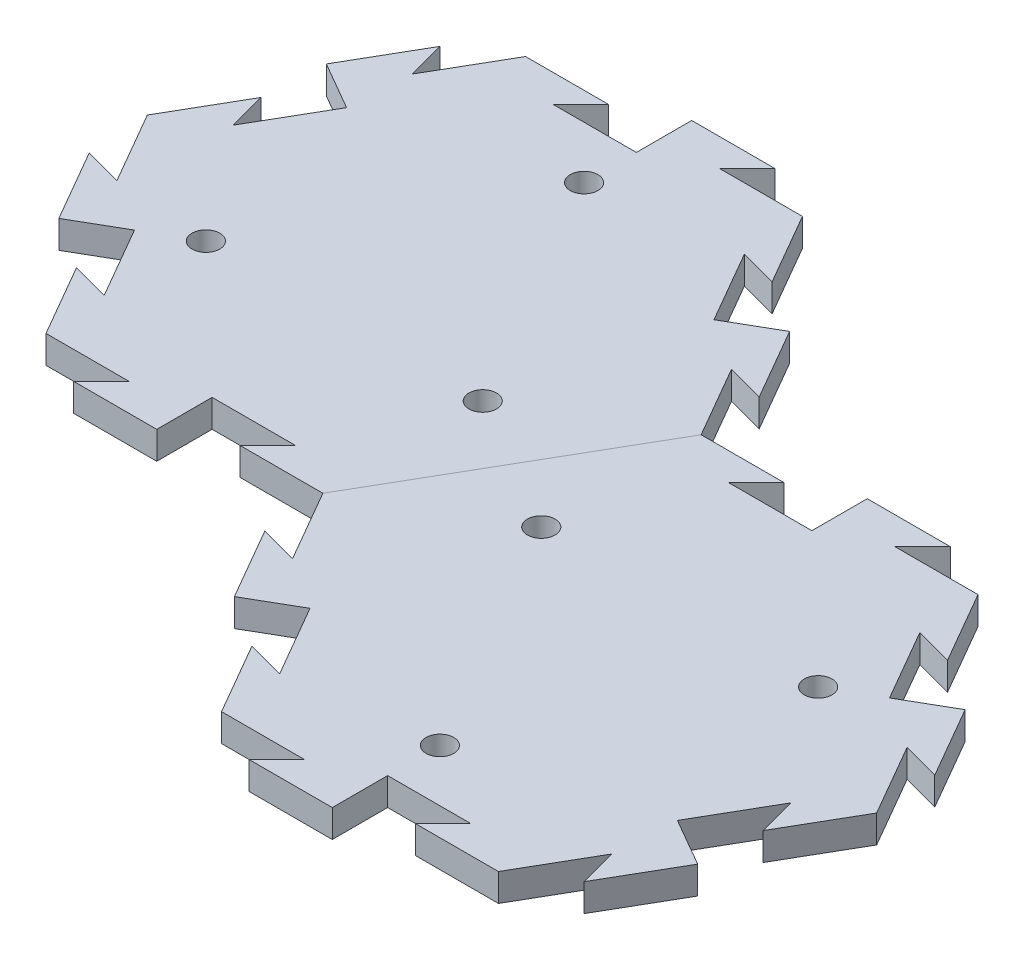
SolidWorks part; units mm, degrees
material "Cedar"
ref_plane "Front Plane" through (0, 0, 0) normal (0, 0, 1) x (1, 0, 0)
ref_plane "Top Plane" through (0, 0, 0) normal (0, 1, 0) x (1, 0, 0)
ref_plane "Right Plane" through (0, 0, 0) normal (1, 0, 0) x (0, 0, -1)
sketch "Sketch1" plane through (0, 0, 0) normal (0, 1, 0) x (1, 0, 0)
  line L0 (0, 0) -> (63.5, 0) construction
  line L1 (63.5, 0) -> (31.75, 54.9926)
  line L2 (31.75, 54.9926) -> (-31.75, 54.9926)
  line L3 (-31.75, 54.9926) -> (-63.5, 0)
  line L4 (-63.5, 0) -> (-31.75, -54.9926)
  line L5 (-31.75, -54.9926) -> (31.75, -54.9926)
  line L6 (31.75, -54.9926) -> (63.5, 0)
  circle A0 centre (0, 0) radius 54.9926 construction
  dimension "D1" = 63.5
extrude "Boss-Extrude1" add sketch "Sketch1" against normal blind 6.35
sketch "Sketch2" plane through (0, 0, 0) normal (0, 1, 0) x (1, 0, 0)
  point P1 (0, 0)
ref_axis "Axis1" through (0, 0, 0) along (0, 1, 0)
sketch "Sketch9" plane through (0, 0, 0) normal (0, 1, 0) x (1, 0, 0)
  line L1 (31.75, -18.3309) -> (0, 36.6617) construction
  line L2 (0, 36.6617) -> (-31.75, -18.3309) construction
  line L3 (-31.75, -18.3309) -> (31.75, -18.3309) construction
  circle A0 centre (0, 0) radius 18.3309 construction
  circle A1 centre (-31.75, -18.3309) radius 3.175
  dimension "D2" = 6.35
  dimension "D1" = 63.5
extrude "Cut-Extrude3" cut sketch "Sketch9" against normal through all
pattern_circular "CirPattern6" count 3 over 360 about axis through (0, 0, 0) along (0, 1, 0) of "Cut-Extrude3"
mirror "Mirror3" about plane through (31.75, -6.35, 54.9926) normal (0.866, 0, 0.5) of bodies 121 125
sketch "Sketch10" plane through (0, 0, 0) normal (0, 1, 0) x (1, 0, 0)
  line L0 (31.75, 54.9926) -> (41.275, 38.4948) construction
  line L1 (41.275, 38.4948) -> (32.6007, 40.8191)
  line L2 (32.6007, 40.8191) -> (42.1257, 24.3213)
  line L3 (42.1257, 24.3213) -> (47.625, 27.4963)
  line L4 (41.275, 38.4948) -> (47.625, 27.4963)
  line L5 (63.5, 0) -> (31.75, 54.9926) construction
  dimension "D1" = 45
  dimension "D2" = 6.35
extrude "Cut-Extrude4" cut sketch "Sketch10" against normal through all
sketch "Sketch11" plane through (0, 0, 0) normal (0, 1, 0) x (1, 0, 0)
  line L0 (47.625, 27.4963) -> (63.5, 0) construction
  line L1 (47.625, 27.4963) -> (53.1243, 30.6713)
  line L2 (53.1243, 30.6713) -> (62.6493, 14.1735)
  line L3 (62.6493, 14.1735) -> (53.975, 16.4978)
  line L4 (53.975, 16.4978) -> (47.625, 27.4963)
  line L5 (53.975, 16.4978) -> (63.5, 0) construction
  line L6 (53.975, 16.4978) -> (63.5, 0) construction
  line L7 (63.5, 0) -> (47.625, 27.4963) construction
  line L8 (31.75, -54.9926) -> (63.5, 0) construction
  dimension "D1" = 45
  dimension "D2" = 6.35
extrude "Boss-Extrude4" add sketch "Sketch11" against normal blind 6.35
pattern_circular "CirPattern7" count 6 over 360 about axis through (0, 0, 0) along (0, 1, 0) skipping 5 of "Cut-Extrude4", "Boss-Extrude4"
sketch "Sketch12" plane through (0, 0, 0) normal (0, 1, 0) x (1, 0, 0)
  line L0 (127, 0) -> (63.5, -109.9852) construction
  point P4 (95.25, -54.9926)
ref_axis "Axis2" through (95.25, 0, 54.9926) along (0, 1, 0)
sketch "Sketch13" plane through (0, 0, 0) normal (0, 1, 0) x (1, 0, 0)
  line L0 (127, 0) -> (136.525, -16.4978) construction
  line L1 (136.525, -16.4978) -> (127.8507, -14.1735)
  line L2 (127.8507, -14.1735) -> (137.3757, -30.6713)
  line L3 (137.3757, -30.6713) -> (142.875, -27.4963)
  line L4 (136.525, -16.4978) -> (142.875, -27.4963)
  line L5 (127, 0) -> (158.75, -54.9926) construction
  dimension "D1" = 45
  dimension "D2" = 6.35
extrude "Cut-Extrude5" cut sketch "Sketch13" against normal through all
sketch "Sketch14" plane through (0, 0, 0) normal (0, 1, 0) x (1, 0, 0)
  line L0 (142.875, -27.4963) -> (158.75, -54.9926) construction
  line L1 (142.875, -27.4963) -> (148.3743, -24.3213)
  line L2 (148.3743, -24.3213) -> (157.8993, -40.8191)
  line L3 (157.8993, -40.8191) -> (149.225, -38.4948)
  line L4 (149.225, -38.4948) -> (142.875, -27.4963)
  line L5 (149.225, -38.4948) -> (158.75, -54.9926) construction
  line L6 (149.225, -38.4948) -> (158.75, -54.9926) construction
  dimension "D1" = 45
  dimension "D2" = 6.35
extrude "Boss-Extrude5" add sketch "Sketch14" against normal blind 6.35
pattern_circular "CirPattern8" count 6 over 360 about axis through (95.25, 0, 54.9926) along (0, 1, 0) skipping 2 of "Cut-Extrude5", "Boss-Extrude5"
